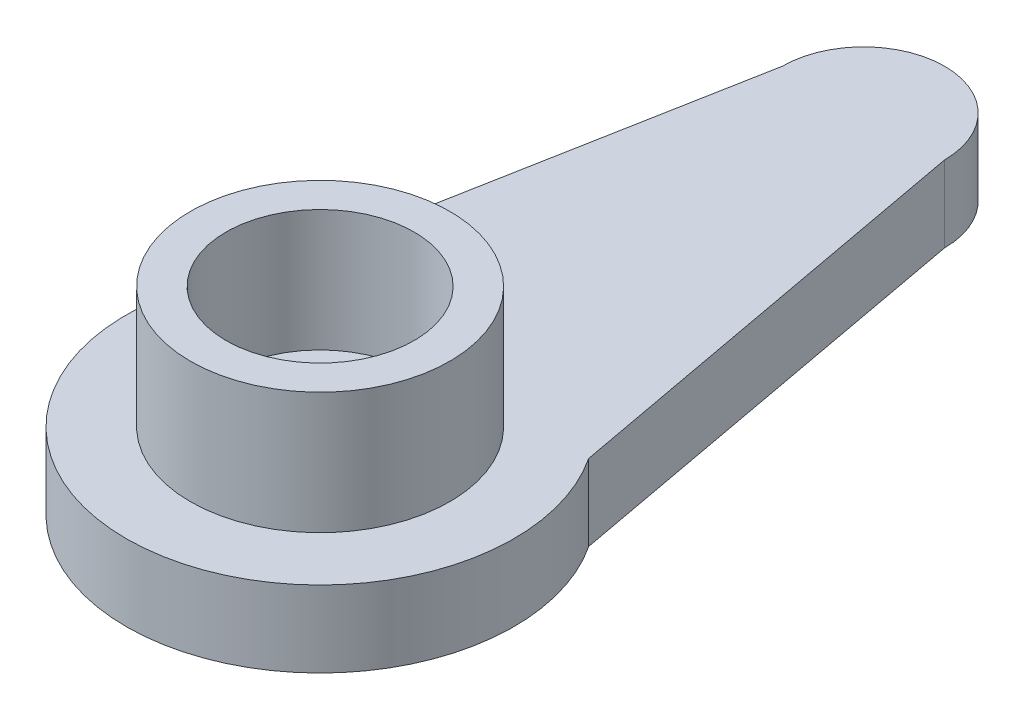
SolidWorks part; units mm, degrees
ref_plane "Front Plane" through (0, 0, 0) normal (0, 0, 1) x (1, 0, 0)
ref_plane "Top Plane" through (0, 0, 0) normal (0, 1, 0) x (1, 0, 0)
ref_plane "Right Plane" through (0, 0, 0) normal (1, 0, 0) x (0, 0, -1)
sketch "Sketch1" plane through (0, 0, 0) normal (0, 1, 0) x (1, 0, 0)
  line L0 (0, 0) -> (0, 19.25) construction
  line L1 (-2.5, 16.75) -> (-5.0155, 3.2474)
  line L2 (2.5, 16.75) -> (4.9844, 3.2948)
  arc A0 (-5.0155, 3.2474) -> (4.9844, 3.2948) centre (0, 0) ccw
  arc A1 (2.5, 16.75) -> (-2.5, 16.75) centre (0, 16.75) ccw
  circle A2 centre (0, 0) radius 1.55
  circle A3 centre (0, 0) radius 2.9
  circle A4 centre (0, 0) radius 4
  dimension "D1" = 11.95
  dimension "D3" = 5
  dimension "D5" = 3.1
  dimension "D6" = 5.8
  dimension "D7" = 8
  dimension "D2" = 19.25
  dimension "D4" = 10
extrude "Boss-Extrude1" add sketch "Sketch1" along normal blind 2.35 contours A4 A1 L1 A0 L2 | A3 A4 | A2 A3 region at (-0.0041, 0, -6.6845) region at (-2.818, 0, 0) region at (-3.8869, 0, 0)
extrude "Boss-Extrude2" add sketch "Sketch1<3>" along normal blind 6.1 contours A3 A4 region at (-3.8869, 0, 0)
sketch "Sketch1<3>" plane through (0, 0, 0) normal (0, 1, 0) x (1, 0, 0) same geometry as "Sketch1"
